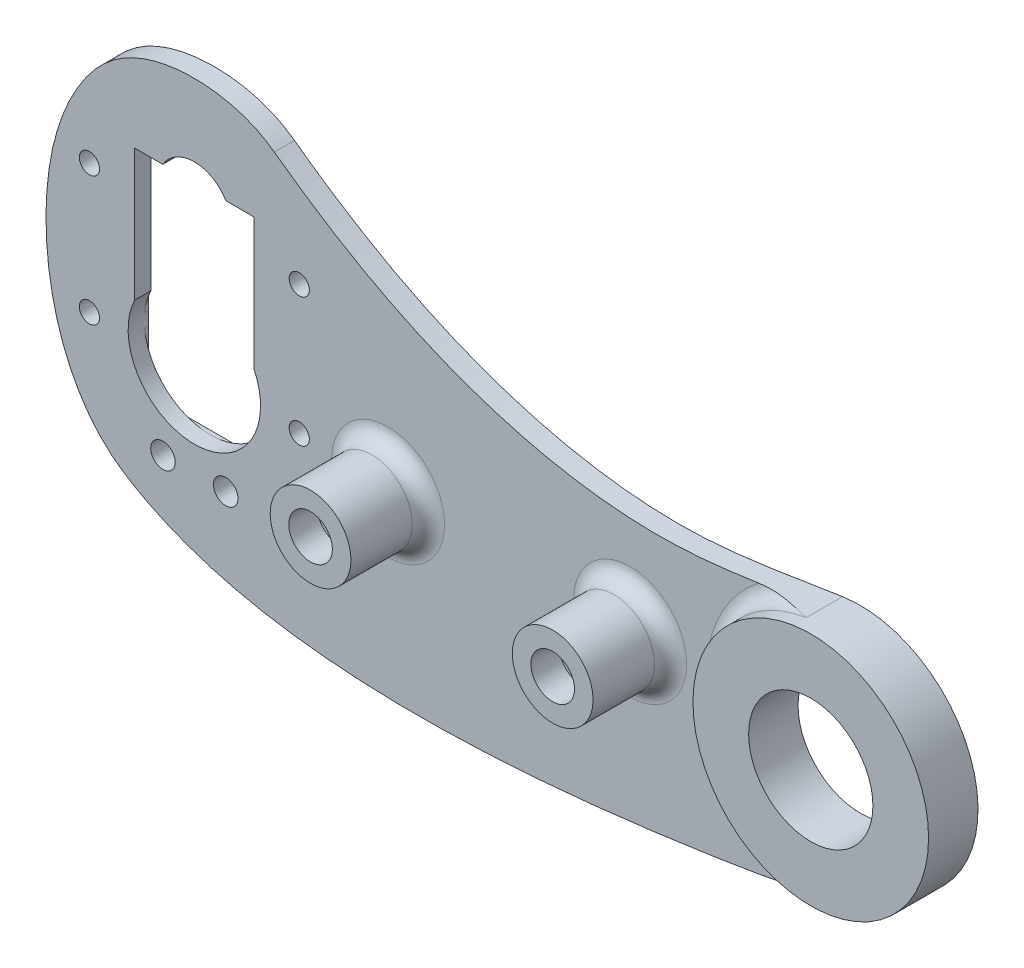
SolidWorks part; units mm, degrees
note: '?' marks a value the reader was unsure of.
ref_plane "Front Plane" through (0, 0, 0) normal (0, 0, 1) x (1, 0, 0)
ref_plane "Top Plane" through (0, 0, 0) normal (0, 1, 0) x (1, 0, 0)
ref_plane "Right Plane" through (0, 0, 0) normal (1, 0, 0) x (0, 0, -1)
sketch "Sketch1" plane through (0, 0, 0) normal (0, 0, 1) x (1, 0, 0)
  line L1 (-59.7576, -2.7999) -> (59.7575, -2.7999) construction
  arc A0 (98.7462, 101.3851) -> (111.9084, 66.5303) centre (101.5997, 82.55) cw
  spline S0 degree 3 poles (12.8847, 120.3395) (20.757, 114.5541) (40.2518, 102.8853) (70.9878, 96.3373) (90.9148, 100.1986) (98.7462, 101.3851) knots 0 0 0 0 0.326633 0.741728 1 1 1 1
  spline S7 degree 3 poles (-11.4525, 64.0459) (8.8535, 50.7358) (59.2076, 53.4213) (104.5778, 61.813) (111.9084, 66.5303) knots 0 0 0 0 0.739683 1 1 1 1
  spline S8 degree 3 poles (-1.8749, 60.7035) (1.8749, 60.7035) (3.711, 60.9284) (5.9539, 61.519) (6.3998, 61.6527) (7.2862, 61.9522) (7.7258, 62.1179) (9.0136, 62.6548) (9.8384, 63.0681) (11.423, 64.0017) (12.1827, 64.5221) (13.2737, 65.3826) (13.6293, 65.6827) (14.3244, 66.3093) (14.6622, 66.6342) (16.2887, 68.2982) (17.41, 69.7686) (18.8777, 72.1399) (19.3317, 72.9613) (20.1584, 74.6261) (20.5332, 75.4725) (21.5561, 78.0488) (22.1035, 79.8152) (22.757, 82.526) (22.9466, 83.4407) (23.269, 85.2688) (23.4024, 86.1848) (23.7252, 88.9383) (23.8375, 90.7812) (23.8583, 93.5559) (23.8405, 94.4825) (23.7536, 96.3394) (23.6842, 97.2698) (23.3967, 100.036) (23.1015, 101.8574) (22.2622, 105.4455) (21.7168, 107.2119) (20.6788, 109.8133) (20.2988, 110.6653) (19.4754, 112.3275) (19.0317, 113.1397) (18.071, 114.7212) (17.555, 115.4909) (16.4308, 116.9762) (15.8182, 117.6943) (13.8675, 119.6805) (12.4021, 120.799) (10.3405, 121.9108) (9.9175, 122.1184) (9.0667, 122.4979) (8.6368, 122.6711) (7.3346, 123.1448) (6.4499, 123.3995) (4.6515, 123.8026) (3.7378, 123.9512) (2.3475, 124.1007) (1.8798, 124.1382) (0.9489, 124.1881) (0.4844, 124.2006) (-0.9061, 124.2017) (-1.8292, 124.1541) (-3.6675, 123.9609) (-4.5827, 123.8155) (-5.9488, 123.513) (-6.4045, 123.3974) (-7.3014, 123.1387) (-7.7438, 122.9953) (-9.0516, 122.5214) (-9.8979, 122.1471) (-11.125, 121.4889) (-11.5269, 121.2534) (-12.316, 120.7487) (-12.7018, 120.4801) (-13.8172, 119.6382) (-14.511, 119.0246) (-15.8096, 117.7038) (-16.4152, 116.9956) (-17.5468, 115.503) (-18.065, 114.7304) (-19.0286, 113.1453) (-19.473, 112.3321) (-20.2967, 110.6699) (-20.6756, 109.8207) (-21.3682, 108.0862) (-21.6789, 107.2076) (-22.2303, 105.4403) (-22.4717, 104.5498) (-23.1011, 101.8593) (-23.3958, 100.0406) (-23.6832, 97.2817) (-23.7525, 96.3567) (-23.8401, 94.4966) (-23.8582, 93.5683) (-23.8381, 90.7933) (-23.7262, 88.9545) (-23.2996, 85.2998) (-22.9853, 83.484) (-22.3374, 80.7801) (-22.0908, 79.8789) (-21.5361, 78.1018) (-21.2287, 77.2271) (-20.2082, 74.6484) (-19.3981, 72.9891) (-17.9359, 70.6142) (-17.4041, 69.8385) (-16.2681, 68.3628) (-15.6623, 67.6597) (-14.3671, 66.3302) (-13.6765, 65.7026) (-12.2066, 64.5387) (-11.4408, 64.013) (-9.8478, 63.0728) (-9.0208, 62.6583) (-7.3047, 61.942) (-6.4104, 61.6395) (-3.7133, 60.9284) (-1.8749, 60.7035) (1.8749, 60.7035) (3.711, 60.9284) knots -0.03125 -0.03125 0 0 0.03125 0.03125 0.039062 0.039062 0.046875 0.046875 0.0625 0.0625 0.078125 0.078125 0.085937 0.085937 0.09375 0.09375 0.125 0.125 0.140625 0.140625 0.15625 0.15625 0.1875 0.1875 0.203125 0.203125 0.21875 0.21875 0.25 0.25 0.265625 0.265625 0.28125 0.28125 0.3125 0.3125 0.34375 0.34375 0.359375 0.359375 0.375 0.375 0.390625 0.390625 0.40625 0.40625 0.4375 0.4375 0.445312 0.445312 0.453125 0.453125 0.46875 0.46875 0.484375 0.484375 0.492187 0.492187 0.5 0.5 0.515625 0.515625 0.53125 0.53125 0.539062 0.539062 0.546875 0.546875 0.5625 0.5625 0.570312 0.570312 0.578125 0.578125 0.59375 0.59375 0.609375 0.609375 0.625 0.625 0.640625 0.640625 0.65625 0.65625 0.671875 0.671875 0.6875 0.6875 0.71875 0.71875 0.734375 0.734375 0.75 0.75 0.78125 0.78125 0.8125 0.8125 0.828125 0.828125 0.84375 0.84375 0.875 0.875 0.890625 0.890625 0.90625 0.90625 0.921875 0.921875 0.9375 0.9375 0.953125 0.953125 0.96875 0.96875 1 1 1.03125 1.03125 1.039062 only from (0, 60.7035) to (0, 60.7035) construction
  spline S9 degree 3 poles (12.8847, 120.3395) (12.2107, 120.8348) (11.5007, 121.2852) (10.3405, 121.9108) (9.9175, 122.1184) (9.0667, 122.4979) (8.6368, 122.6711) (7.3346, 123.1448) (6.4499, 123.3995) (4.6515, 123.8026) (3.7378, 123.9512) (2.3475, 124.1007) (1.8798, 124.1382) (0.9489, 124.1881) (0.4844, 124.2006) (-0.9061, 124.2017) (-1.8292, 124.1541) (-3.6675, 123.9609) (-4.5827, 123.8155) (-5.9488, 123.513) (-6.4045, 123.3974) (-7.3014, 123.1387) (-7.7438, 122.9953) (-9.0516, 122.5214) (-9.8979, 122.1471) (-11.125, 121.4889) (-11.5269, 121.2534) (-12.316, 120.7487) (-12.7018, 120.4801) (-13.8172, 119.6382) (-14.511, 119.0246) (-15.8096, 117.7038) (-16.4152, 116.9956) (-17.5468, 115.503) (-18.065, 114.7304) (-19.0286, 113.1453) (-19.473, 112.3321) (-20.2967, 110.6699) (-20.6756, 109.8207) (-21.3682, 108.0862) (-21.6789, 107.2076) (-22.2303, 105.4403) (-22.4717, 104.5498) (-23.1011, 101.8593) (-23.3958, 100.0406) (-23.6832, 97.2817) (-23.7525, 96.3567) (-23.8401, 94.4966) (-23.8582, 93.5683) (-23.8381, 90.7933) (-23.7262, 88.9545) (-23.2996, 85.2998) (-22.9853, 83.484) (-22.3374, 80.7801) (-22.0908, 79.8789) (-21.5361, 78.1018) (-21.2287, 77.2271) (-20.2082, 74.6484) (-19.3981, 72.9891) (-17.9359, 70.6142) (-17.4041, 69.8385) (-16.2681, 68.3628) (-15.6623, 67.6597) (-14.3671, 66.3302) (-13.6765, 65.7026) (-12.4585, 64.7382) (-11.9621, 64.38) (-11.4525, 64.0459) knots 0.42333 0.42333 0.42333 0.42333 0.4375 0.4375 0.445312 0.445312 0.453125 0.453125 0.46875 0.46875 0.484375 0.484375 0.492187 0.492187 0.5 0.5 0.515625 0.515625 0.53125 0.53125 0.539062 0.539062 0.546875 0.546875 0.5625 0.5625 0.570312 0.570312 0.578125 0.578125 0.59375 0.59375 0.609375 0.609375 0.625 0.625 0.640625 0.640625 0.65625 0.65625 0.671875 0.671875 0.6875 0.6875 0.71875 0.71875 0.734375 0.734375 0.75 0.75 0.78125 0.78125 0.8125 0.8125 0.828125 0.828125 0.84375 0.84375 0.875 0.875 0.890625 0.890625 0.90625 0.90625 0.921875 0.921875 0.932145 0.932145 0.932145 0.932145
  dimension "D1" = 101.6
  dimension "D3" = 19.05
  dimension "D2" = 85.3499
extrude "Boss-Extrude1" add sketch "Sketch1" along normal blind 3.175
hole_wizard "1/8 (0.125) Diameter Hole1" positions "Sketch2" profile "Sketch3" hole size "1/8" standard "ANSI Inch" end condition through all
sketch "Sketch2" plane through (0, 0, 3.175) normal (0, 0, 1) x (1, 0, 0)
  line L0 (0, -8.7367) -> (0, 8.7367) construction
  line L1 (0, 124.201) -> (0, 58.6164) construction
  spline S0 degree 3 poles (12.8847, 120.3395) (12.2107, 120.8348) (11.5007, 121.2852) (10.3405, 121.9108) (9.9175, 122.1184) (9.0667, 122.4979) (8.6368, 122.6711) (7.3346, 123.1448) (6.4499, 123.3995) (4.6515, 123.8026) (3.7378, 123.9512) (2.3475, 124.1007) (1.8798, 124.1382) (0.9489, 124.1881) (0.4844, 124.2006) (-0.9061, 124.2017) (-1.8292, 124.1541) (-3.6675, 123.9609) (-4.5827, 123.8155) (-5.9488, 123.513) (-6.4045, 123.3974) (-7.3014, 123.1387) (-7.7438, 122.9953) (-9.0516, 122.5214) (-9.8979, 122.1471) (-11.125, 121.4889) (-11.5269, 121.2534) (-12.316, 120.7487) (-12.7018, 120.4801) (-13.8172, 119.6382) (-14.511, 119.0246) (-15.8096, 117.7038) (-16.4152, 116.9956) (-17.5468, 115.503) (-18.065, 114.7304) (-19.0286, 113.1453) (-19.473, 112.3321) (-20.2967, 110.6699) (-20.6756, 109.8207) (-21.3682, 108.0862) (-21.6789, 107.2076) (-22.2303, 105.4403) (-22.4717, 104.5498) (-23.1011, 101.8593) (-23.3958, 100.0406) (-23.6832, 97.2817) (-23.7525, 96.3567) (-23.8401, 94.4966) (-23.8582, 93.5683) (-23.8381, 90.7933) (-23.7262, 88.9545) (-23.2996, 85.2998) (-22.9853, 83.484) (-22.3374, 80.7801) (-22.0908, 79.8789) (-21.5361, 78.1018) (-21.2287, 77.2271) (-20.2082, 74.6484) (-19.3981, 72.9891) (-17.9359, 70.6142) (-17.4041, 69.8385) (-16.2681, 68.3628) (-15.6623, 67.6597) (-14.3671, 66.3302) (-13.6765, 65.7026) (-12.4585, 64.7382) (-11.9621, 64.38) (-11.4525, 64.0459) knots 0.42333 0.42333 0.42333 0.42333 0.4375 0.4375 0.445312 0.445312 0.453125 0.453125 0.46875 0.46875 0.484375 0.484375 0.492187 0.492187 0.5 0.5 0.515625 0.515625 0.53125 0.53125 0.539062 0.539062 0.546875 0.546875 0.5625 0.5625 0.570312 0.570312 0.578125 0.578125 0.59375 0.59375 0.609375 0.609375 0.625 0.625 0.640625 0.640625 0.65625 0.65625 0.671875 0.671875 0.6875 0.6875 0.71875 0.71875 0.734375 0.734375 0.75 0.75 0.78125 0.78125 0.8125 0.8125 0.828125 0.828125 0.84375 0.84375 0.875 0.875 0.890625 0.890625 0.90625 0.90625 0.921875 0.921875 0.932145 0.932145 0.932145 0.932145 construction
  spline S1 degree 3 poles (-11.4525, 64.0459) (8.8535, 50.7358) (59.2076, 53.4213) (104.5778, 61.813) (111.9084, 66.5303) knots 0 0 0 0 0.739683 1 1 1 1 construction
  point P28 (16.51, 103.881)
  point P30 (16.51, 83.561)
  point P32 (-16.51, 83.561)
  point P61 (-16.51, 103.881)
  dimension "D1" = 16.51
  dimension "D2" = 20.32
  dimension "D3" = 16.51
  dimension "D4" = 20.32
sketch "Sketch3" plane through (-16.51, 103.881, 3.175) normal (1, 0, 0) x (0, -1, 0)
  line L0 (0, 0) -> (0, 3.175)
  line L1 (0, 3.175) -> (1.5875, 3.175)
  line L2 (1.5875, 3.175) -> (1.5875, 0)
  line L5 (1.5875, 0) -> (0, 0)
  line L11 (0, -6.35) -> (0, 107.95) construction
  dimension "Thru Hole Dia." = 3.175
  dimension "Thru Hole Depth" = 3.175
sketch "Sketch7" plane through (0, 0, 0) normal (0, 0, -1) x (-1, 0, 0)
  line L1 (9.0932, 115.311) -> (-9.0932, 115.311)
  line L2 (10.3632, 114.041) -> (10.3632, 75.1028)
  line L3 (9.0932, 73.8328) -> (-9.0932, 73.8328)
  line L4 (-10.3632, 114.041) -> (-10.3632, 75.1028)
  line L5 (0, 124.201) -> (0, 60.7035) construction
  line L6 (0, 8.7367) -> (0, -8.7367) construction
  arc A0 (9.0932, 115.311) -> (10.3632, 114.041) centre (9.0932, 114.041) cw
  arc A1 (10.3632, 75.1028) -> (9.0932, 73.8328) centre (9.0932, 75.1028) cw
  arc A2 (-9.0932, 73.8328) -> (-10.3632, 75.1028) centre (-9.0932, 75.1028) cw
  arc A3 (-9.0932, 115.311) -> (-10.3632, 114.041) centre (-9.0932, 114.041) ccw
  spline S0 degree 3 poles (-12.8847, 120.3395) (-12.2107, 120.8348) (-11.5007, 121.2852) (-10.3405, 121.9108) (-9.9175, 122.1184) (-9.0667, 122.4979) (-8.6368, 122.6711) (-7.3346, 123.1448) (-6.4499, 123.3995) (-4.6515, 123.8026) (-3.7378, 123.9512) (-2.3475, 124.1007) (-1.8798, 124.1382) (-0.9489, 124.1881) (-0.4844, 124.2006) (0.9061, 124.2017) (1.8292, 124.1541) (3.6675, 123.9609) (4.5827, 123.8155) (5.9488, 123.513) (6.4045, 123.3974) (7.3014, 123.1387) (7.7438, 122.9953) (9.0516, 122.5214) (9.8979, 122.1471) (11.125, 121.4889) (11.5269, 121.2534) (12.316, 120.7487) (12.7018, 120.4801) (13.8172, 119.6382) (14.511, 119.0246) (15.8096, 117.7038) (16.4152, 116.9956) (17.5468, 115.503) (18.065, 114.7304) (19.0286, 113.1453) (19.473, 112.3321) (20.2967, 110.6699) (20.6756, 109.8207) (21.3682, 108.0862) (21.6789, 107.2076) (22.2303, 105.4403) (22.4717, 104.5498) (23.1011, 101.8593) (23.3958, 100.0406) (23.6832, 97.2817) (23.7525, 96.3567) (23.8401, 94.4966) (23.8582, 93.5683) (23.8381, 90.7933) (23.7262, 88.9545) (23.2996, 85.2998) (22.9853, 83.484) (22.3374, 80.7801) (22.0908, 79.8789) (21.5361, 78.1018) (21.2287, 77.2271) (20.2082, 74.6484) (19.3981, 72.9891) (17.9359, 70.6142) (17.4041, 69.8385) (16.2681, 68.3628) (15.6623, 67.6597) (14.3671, 66.3302) (13.6765, 65.7026) (12.4585, 64.7382) (11.9621, 64.38) (11.4525, 64.0459) knots 0.42333 0.42333 0.42333 0.42333 0.4375 0.4375 0.445312 0.445312 0.453125 0.453125 0.46875 0.46875 0.484375 0.484375 0.492187 0.492187 0.5 0.5 0.515625 0.515625 0.53125 0.53125 0.539062 0.539062 0.546875 0.546875 0.5625 0.5625 0.570312 0.570312 0.578125 0.578125 0.59375 0.59375 0.609375 0.609375 0.625 0.625 0.640625 0.640625 0.65625 0.65625 0.671875 0.671875 0.6875 0.6875 0.71875 0.71875 0.734375 0.734375 0.75 0.75 0.78125 0.78125 0.8125 0.8125 0.828125 0.828125 0.84375 0.84375 0.875 0.875 0.890625 0.890625 0.90625 0.90625 0.921875 0.921875 0.932145 0.932145 0.932145 0.932145 construction
  spline S2 degree 3 poles (-1.8749, 60.7035) (1.8749, 60.7035) (3.7133, 60.9284) (6.4104, 61.6395) (7.3047, 61.942) (9.0208, 62.6583) (9.8478, 63.0728) (11.4408, 64.013) (12.2066, 64.5387) (13.6765, 65.7026) (14.3671, 66.3302) (15.6623, 67.6597) (16.2681, 68.3628) (17.4041, 69.8385) (17.9359, 70.6142) (19.3981, 72.9891) (20.2082, 74.6484) (21.2287, 77.2271) (21.5361, 78.1018) (22.0908, 79.8789) (22.3374, 80.7801) (22.9853, 83.484) (23.2996, 85.2998) (23.7262, 88.9545) (23.8381, 90.7933) (23.8582, 93.5683) (23.8401, 94.4966) (23.7525, 96.3567) (23.6832, 97.2817) (23.3958, 100.0406) (23.1011, 101.8593) (22.4717, 104.5498) (22.2303, 105.4403) (21.6789, 107.2076) (21.3682, 108.0862) (20.6756, 109.8207) (20.2967, 110.6699) (19.473, 112.3321) (19.0286, 113.1453) (18.065, 114.7304) (17.5468, 115.503) (16.4152, 116.9956) (15.8096, 117.7038) (14.511, 119.0246) (13.8172, 119.6382) (12.7018, 120.4801) (12.316, 120.7487) (11.5269, 121.2534) (11.125, 121.4889) (9.8979, 122.1471) (9.0516, 122.5214) (7.7438, 122.9953) (7.3014, 123.1387) (6.4045, 123.3974) (5.9488, 123.513) (4.5827, 123.8155) (3.6675, 123.9609) (1.8292, 124.1541) (0.9061, 124.2017) (-0.4844, 124.2006) (-0.9489, 124.1881) (-1.8798, 124.1382) (-2.3475, 124.1007) (-3.7378, 123.9512) (-4.6515, 123.8026) (-6.4499, 123.3995) (-7.3346, 123.1448) (-8.6368, 122.6711) (-9.0667, 122.4979) (-9.9175, 122.1184) (-10.3405, 121.9108) (-12.4021, 120.799) (-13.8675, 119.6805) (-15.8182, 117.6943) (-16.4308, 116.9762) (-17.555, 115.4909) (-18.071, 114.7212) (-19.0317, 113.1397) (-19.4754, 112.3275) (-20.2988, 110.6653) (-20.6788, 109.8133) (-21.7168, 107.2119) (-22.2622, 105.4455) (-23.1015, 101.8574) (-23.3967, 100.036) (-23.6842, 97.2698) (-23.7536, 96.3394) (-23.8405, 94.4825) (-23.8583, 93.5559) (-23.8375, 90.7812) (-23.7252, 88.9383) (-23.4024, 86.1848) (-23.269, 85.2688) (-22.9466, 83.4407) (-22.757, 82.526) (-22.1035, 79.8152) (-21.5561, 78.0488) (-20.5332, 75.4725) (-20.1584, 74.6261) (-19.3317, 72.9613) (-18.8777, 72.1399) (-17.41, 69.7686) (-16.2887, 68.2982) (-14.6622, 66.6342) (-14.3244, 66.3093) (-13.6293, 65.6827) (-13.2737, 65.3826) (-12.1827, 64.5221) (-11.423, 64.0017) (-9.8384, 63.0681) (-9.0136, 62.6548) (-7.7258, 62.1179) (-7.2862, 61.9522) (-6.3998, 61.6527) (-5.9539, 61.519) (-3.711, 60.9284) (-1.8749, 60.7035) (1.8749, 60.7035) (3.7133, 60.9284) knots -0.03125 -0.03125 0 0 0.03125 0.03125 0.046875 0.046875 0.0625 0.0625 0.078125 0.078125 0.09375 0.09375 0.109375 0.109375 0.125 0.125 0.15625 0.15625 0.171875 0.171875 0.1875 0.1875 0.21875 0.21875 0.25 0.25 0.265625 0.265625 0.28125 0.28125 0.3125 0.3125 0.328125 0.328125 0.34375 0.34375 0.359375 0.359375 0.375 0.375 0.390625 0.390625 0.40625 0.40625 0.421875 0.421875 0.429688 0.429688 0.4375 0.4375 0.453125 0.453125 0.460938 0.460938 0.46875 0.46875 0.484375 0.484375 0.5 0.5 0.507813 0.507813 0.515625 0.515625 0.53125 0.53125 0.546875 0.546875 0.554688 0.554688 0.5625 0.5625 0.59375 0.59375 0.609375 0.609375 0.625 0.625 0.640625 0.640625 0.65625 0.65625 0.6875 0.6875 0.71875 0.71875 0.734375 0.734375 0.75 0.75 0.78125 0.78125 0.796875 0.796875 0.8125 0.8125 0.84375 0.84375 0.859375 0.859375 0.875 0.875 0.90625 0.90625 0.914063 0.914063 0.921875 0.921875 0.9375 0.9375 0.953125 0.953125 0.960938 0.960938 0.96875 0.96875 1 1 1.03125 1.03125 1.046875 only from (0, 60.7035) to (0, 60.7035) construction
  point P24 (0, 115.311)
  dimension "D3" = 1.27
  dimension "D1" = 41.4782
  dimension "D2" = 20.7264
  dimension "D4" = 8.89
extrude "Cut-Extrude3" cut sketch "Sketch7" against normal blind 0.635
sketch "Sketch8" plane through (0, 0, 3.175) normal (0, 0, 1) x (1, 0, 0)
  line L0 (0, -8.7367) -> (0, 8.7367) construction
  line L1 (-9.0932, 73.8328) -> (9.0932, 73.8328) construction
  line L20 (-4.9585, 109.4888) -> (-9.388, 109.4888)
  line L21 (-9.388, 109.4888) -> (-9.388, 88.7675)
  line L22 (9.388, 88.7675) -> (9.388, 109.4888)
  line L23 (9.388, 109.4888) -> (4.9585, 109.4888)
  arc A13 (-9.388, 88.7675) -> (9.388, 88.7675) centre (0, 84.2508) ccw
  arc A14 (4.9585, 109.4888) -> (-4.9585, 109.4888) centre (0, 106.5508) ccw
  dimension "D1" = 5.7635
  dimension "D2" = 10.418
  dimension "D3" = 25.238
  dimension "D4" = 18.776
  dimension "D5" = 2.938
extrude "Cut-Extrude4" cut sketch "Sketch8" against normal through all
sketch "Sketch10" plane through (0, 0, 0) normal (0, 0, -1) x (-1, 0, 0)
  circle A0 centre (-101.5997, 82.55) radius 9.779
  dimension "D1" = 19.558
extrude "Cut-Extrude5" cut sketch "Sketch10" against normal through all
hole_wizard "Hole1" positions "Sketch12" profile "Sketch13" legacy
sketch "Sketch12" plane through (0, 0, 0) normal (0, 0, -1) x (-1, 0, 0)
  point P0 (-4.935, 69.8508)
  point P3 (4.935, 69.8508)
sketch "Sketch13" plane through (4.935, 69.8508, 0) normal (1, 0, 0) x (0, 1, 0)
  line L0 (0, 0) -> (0, 8.255)
  line L1 (0, 8.255) -> (1.5875, 8.255)
  line L2 (1.5875, 8.255) -> (1.5875, 5.1562)
  line L3 (1.5875, 5.1562) -> (1.9304, 5.1562)
  line L4 (1.9304, 5.1562) -> (1.9304, 0)
  line L5 (1.9304, 0) -> (0, 0)
  line L6 (0, 110) -> (0, -10) construction
  dimension "Diameter" = 3.175
  dimension "Depth" = 8.255
  dimension "C-Bore Diameter" = 3.8608
  dimension "C-Bore Depth" = 5.1562
sketch "Sketch16" plane through (0, 0, 0) normal (0, 0, -1) x (-1, 0, 0)
  arc A1 (-98.7462, 101.3851) -> (-111.9084, 66.5303) centre (-101.5997, 82.55) ccw construction
  arc A2 (-98.8223, 100.8828) -> (-111.6335, 66.9574) centre (-101.5997, 82.55) ccw
  arc A3 (-98.8223, 100.8828) -> (-111.6335, 66.9574) centre (-101.5997, 82.55) ccw
  arc A4 (-98.7462, 101.3851) -> (-111.9084, 66.5303) centre (-101.5997, 82.55) ccw
  spline S3 degree 3 poles (1.8749, 60.7035) (-1.8749, 60.7035) (-3.711, 60.9284) (-5.9539, 61.519) (-6.3998, 61.6527) (-7.2862, 61.9522) (-7.7258, 62.1179) (-9.0136, 62.6548) (-9.8384, 63.0681) (-11.423, 64.0017) (-12.1827, 64.5221) (-13.2737, 65.3826) (-13.6293, 65.6827) (-14.3244, 66.3093) (-14.6622, 66.6342) (-16.2887, 68.2982) (-17.41, 69.7686) (-18.8777, 72.1399) (-19.3317, 72.9613) (-20.1584, 74.6261) (-20.5332, 75.4725) (-21.5561, 78.0488) (-22.1035, 79.8152) (-22.757, 82.526) (-22.9466, 83.4407) (-23.269, 85.2688) (-23.4024, 86.1848) (-23.7252, 88.9383) (-23.8375, 90.7812) (-23.8583, 93.5559) (-23.8405, 94.4825) (-23.7536, 96.3394) (-23.6842, 97.2698) (-23.3967, 100.036) (-23.1015, 101.8574) (-22.2622, 105.4455) (-21.7168, 107.2119) (-20.6788, 109.8133) (-20.2988, 110.6653) (-19.4754, 112.3275) (-19.0317, 113.1397) (-18.071, 114.7212) (-17.555, 115.4909) (-16.4308, 116.9762) (-15.8182, 117.6943) (-13.8675, 119.6805) (-12.4021, 120.799) (-10.3405, 121.9108) (-9.9175, 122.1184) (-9.0667, 122.4979) (-8.6368, 122.6711) (-7.3346, 123.1448) (-6.4499, 123.3995) (-4.6515, 123.8026) (-3.7378, 123.9512) (-2.3475, 124.1007) (-1.8798, 124.1382) (-0.9489, 124.1881) (-0.4844, 124.2006) (0.9061, 124.2017) (1.8292, 124.1541) (3.6675, 123.9609) (4.5827, 123.8155) (5.9488, 123.513) (6.4045, 123.3974) (7.3014, 123.1387) (7.7438, 122.9953) (9.0516, 122.5214) (9.8979, 122.1471) (11.125, 121.4889) (11.5269, 121.2534) (12.316, 120.7487) (12.7018, 120.4801) (13.8172, 119.6382) (14.511, 119.0246) (15.8096, 117.7038) (16.4152, 116.9956) (17.5468, 115.503) (18.065, 114.7304) (19.0286, 113.1453) (19.473, 112.3321) (20.2967, 110.6699) (20.6756, 109.8207) (21.3682, 108.0862) (21.6789, 107.2076) (22.2303, 105.4403) (22.4717, 104.5498) (23.1011, 101.8593) (23.3958, 100.0406) (23.6832, 97.2817) (23.7525, 96.3567) (23.8401, 94.4966) (23.8582, 93.5683) (23.8381, 90.7933) (23.7262, 88.9545) (23.2996, 85.2998) (22.9853, 83.484) (22.3374, 80.7801) (22.0908, 79.8789) (21.5361, 78.1018) (21.2287, 77.2271) (20.2082, 74.6484) (19.3981, 72.9891) (17.9359, 70.6142) (17.4041, 69.8385) (16.2681, 68.3628) (15.6623, 67.6597) (14.3671, 66.3302) (13.6765, 65.7026) (12.2066, 64.5387) (11.4408, 64.013) (9.8478, 63.0728) (9.0208, 62.6583) (7.3047, 61.942) (6.4104, 61.6395) (3.7133, 60.9284) (1.8749, 60.7035) (-1.8749, 60.7035) (-3.711, 60.9284) knots -0.03125 -0.03125 0 0 0.03125 0.03125 0.039062 0.039062 0.046875 0.046875 0.0625 0.0625 0.078125 0.078125 0.085937 0.085937 0.09375 0.09375 0.125 0.125 0.140625 0.140625 0.15625 0.15625 0.1875 0.1875 0.203125 0.203125 0.21875 0.21875 0.25 0.25 0.265625 0.265625 0.28125 0.28125 0.3125 0.3125 0.34375 0.34375 0.359375 0.359375 0.375 0.375 0.390625 0.390625 0.40625 0.40625 0.4375 0.4375 0.445312 0.445312 0.453125 0.453125 0.46875 0.46875 0.484375 0.484375 0.492187 0.492187 0.5 0.5 0.515625 0.515625 0.53125 0.53125 0.539062 0.539062 0.546875 0.546875 0.5625 0.5625 0.570312 0.570312 0.578125 0.578125 0.59375 0.59375 0.609375 0.609375 0.625 0.625 0.640625 0.640625 0.65625 0.65625 0.671875 0.671875 0.6875 0.6875 0.71875 0.71875 0.734375 0.734375 0.75 0.75 0.78125 0.78125 0.8125 0.8125 0.828125 0.828125 0.84375 0.84375 0.875 0.875 0.890625 0.890625 0.90625 0.90625 0.921875 0.921875 0.9375 0.9375 0.953125 0.953125 0.96875 0.96875 1 1 1.03125 1.03125 1.039062 only from (-12.8847, 120.3395) to (11.4525, 64.0459) construction
  spline S4 degree 3 poles (-774.2713, -1774.5433) (-240.5791, 269.0945) (-155.3516, 78.3647) (119.4613, 136.9101) (90.2802, 612.3789) (-467.9203, -1827.1495) knots -2.744785 -2.744785 -2.744785 -2.744785 0.258272 0.673367 6.196281 6.196281 6.196281 6.196281 only from (-98.7462, 101.3851) to (-12.8847, 120.3395) construction
  spline S5 degree 3 poles (-1432.2891, 1438.8419) (302.1687, 78.3883) (-46.8302, 8.2524) (-247.2516, 108.2293) (1573.9405, 1138.8243) knots -2.721752 -2.721752 -2.721752 -2.721752 0.739683 2.738287 2.738287 2.738287 2.738287 only from (11.4525, 64.0459) to (-111.9084, 66.5303) construction
  spline S6 degree 3 poles (-2189.0847, 2099.4129) (-262.4106, 170.4677) (-28.1678, 19.131) (15.6659, 68.4561) (15.964, 68.8125) (16.5416, 69.5447) (16.8215, 69.9212) (17.625, 71.0645) (18.1161, 71.8495) (19.4736, 74.2635) (20.2235, 75.952) (21.0047, 78.1423) (21.1532, 78.5852) (21.4331, 79.4725) (21.5646, 79.9175) (21.9359, 81.2558) (22.1523, 82.1528) (22.7169, 84.8568) (22.9808, 86.6766) (23.227, 89.4293) (23.2837, 90.3507) (23.3467, 92.2012) (23.3532, 93.1331) (23.2962, 95.9153) (23.1579, 97.7528) (22.6664, 101.3907) (22.3118, 103.1909) (21.5787, 105.8563) (21.3007, 106.739) (20.8285, 108.0535) (20.6616, 108.4909) (20.3114, 109.3557) (20.128, 109.7836) (19.5526, 111.0538) (19.1362, 111.8829) (18.2322, 113.5028) (17.7449, 114.2937) (16.9487, 115.445) (16.6714, 115.8238) (16.0972, 116.5601) (15.8001, 116.9181) (14.876, 117.9587) (14.2159, 118.6078) (13.1501, 119.5046) (12.7822, 119.7907) (12.0198, 120.3359) (11.6269, 120.5937) (10.4299, 121.3129) (9.6011, 121.7248) (8.316, 122.2507) (7.8807, 122.4106) (6.9967, 122.7012) (6.5467, 122.8322) (5.1865, 123.1808) (4.2742, 123.353) (2.4403, 123.5949) (1.5188, 123.6652) (0.1298, 123.6968) (-0.3342, 123.695) (-1.2647, 123.6664) (-1.7324, 123.6393) (-3.1284, 123.5203) (-4.0462, 123.3914) (-5.8547, 123.0273) (-6.7453, 122.7922) (-8.0574, 122.347) (-8.4908, 122.1832) (-9.349, 121.8219) (-9.7752, 121.6237) (-90.4408, 80.1939) (184.1635, -546.8682) (1304.7176, -2570.5597) knots -2.147593 -2.147593 -2.147593 -2.147593 0.0625 0.0625 0.078125 0.078125 0.09375 0.09375 0.125 0.125 0.1875 0.1875 0.203125 0.203125 0.21875 0.21875 0.25 0.25 0.3125 0.3125 0.34375 0.34375 0.375 0.375 0.4375 0.4375 0.5 0.5 0.53125 0.53125 0.546875 0.546875 0.5625 0.5625 0.59375 0.59375 0.625 0.625 0.640625 0.640625 0.65625 0.65625 0.6875 0.6875 0.703125 0.703125 0.71875 0.71875 0.75 0.75 0.765625 0.765625 0.78125 0.78125 0.8125 0.8125 0.84375 0.84375 0.859375 0.859375 0.875 0.875 0.90625 0.90625 0.9375 0.9375 0.953125 0.953125 0.96875 0.96875 3.969871 3.969871 3.969871 3.969871 only from (11.174, 64.4708) to (-12.5838, 119.9301)
  spline S7 degree 3 poles (2048.6103, -1983.426) (58.7248, 829.8593) (166.9256, 229.9139) (-23.7272, 112.5017) (-25.3772, 111.5351) (-28.7252, 109.6798) (-30.4244, 108.7904) (-35.592, 106.2537) (-39.095, 104.7565) (-46.2251, 102.1769) (-49.851, 101.091) (-55.3885, 99.7916) (-57.2508, 99.4137) (-60.0708, 98.9354) (-61.0153, 98.7908) (-62.9133, 98.5324) (-63.8683, 98.4185) (-68.6518, 97.9313) (-72.4591, 97.8086) (-179.3835, 102.4579) (-267.4227, 313.3667) (-602.151, -2848.3137) knots -7.132024 -7.132024 -7.132024 -7.132024 0.125 0.125 0.1875 0.1875 0.25 0.25 0.375 0.375 0.5 0.5 0.5625 0.5625 0.59375 0.59375 0.625 0.625 0.75 0.75 4.155026 4.155026 4.155026 4.155026 only from (-12.5838, 119.9301) to (-98.8223, 100.8828)
  spline S8 degree 3 poles (673.853, 2960.0442) (-168.6133, 212.6667) (-155.2694, 87.1083) (-106.9518, 64.4911) (-105.74, 64.0012) (-103.2866, 63.1129) (-102.0449, 62.7149) (-99.5398, 61.9849) (-98.2764, 61.6531) (-94.4623, 60.7311) (-91.8866, 60.2126) (-86.7077, 59.2798) (-84.112, 58.8676) (-76.317, 57.6978) (-71.1112, 56.9962) (-60.6752, 55.803) (-55.4449, 55.3117) (-47.5738, 54.7964) (-44.9429, 54.6617) (-39.6919, 54.4826) (-37.0705, 54.4379) (-31.8374, 54.4562) (-29.2258, 54.519) (-24.0146, 54.776) (-21.4149, 54.97) (-16.2307, 55.5229) (-13.6461, 55.8814) (-8.4964, 56.813) (-5.9312, 57.3853) (-2.1037, 58.4645) (-0.8268, 58.8631) (1.6873, 59.7383) (2.9262, 60.2151) (81.3748, 93.829) (75.8831, 305.7868) (-1020.3508, 2876.1977) knots -1.206471 -1.206471 -1.206471 -1.206471 0.03125 0.03125 0.0625 0.0625 0.09375 0.09375 0.125 0.125 0.1875 0.1875 0.25 0.25 0.375 0.375 0.5 0.5 0.5625 0.5625 0.625 0.625 0.6875 0.6875 0.75 0.75 0.8125 0.8125 0.875 0.875 0.90625 0.90625 0.9375 0.9375 2.918904 2.918904 2.918904 2.918904 only from (-111.6335, 66.9574) to (11.174, 64.4708)
  spline S9 degree 3 poles (11.174, 64.4708) (12.7439, 65.4998) (14.1273, 66.7247) (15.6659, 68.4561) (15.964, 68.8125) (16.5416, 69.5447) (16.8215, 69.9212) (17.625, 71.0645) (18.1161, 71.8495) (19.4736, 74.2635) (20.2235, 75.952) (21.0047, 78.1423) (21.1532, 78.5852) (21.4331, 79.4725) (21.5646, 79.9175) (21.9359, 81.2558) (22.1523, 82.1528) (22.7169, 84.8568) (22.9808, 86.6766) (23.227, 89.4293) (23.2837, 90.3507) (23.3467, 92.2012) (23.3532, 93.1331) (23.2962, 95.9153) (23.1579, 97.7528) (22.6664, 101.3907) (22.3118, 103.1909) (21.5787, 105.8563) (21.3007, 106.739) (20.8285, 108.0535) (20.6616, 108.4909) (20.3114, 109.3557) (20.128, 109.7836) (19.5526, 111.0538) (19.1362, 111.8829) (18.2322, 113.5028) (17.7449, 114.2937) (16.9487, 115.445) (16.6714, 115.8238) (16.0972, 116.5601) (15.8001, 116.9181) (14.876, 117.9587) (14.2159, 118.6078) (13.1501, 119.5046) (12.7822, 119.7907) (12.0198, 120.3359) (11.6269, 120.5937) (10.4299, 121.3129) (9.6011, 121.7248) (8.316, 122.2507) (7.8807, 122.4106) (6.9967, 122.7012) (6.5467, 122.8322) (5.1865, 123.1808) (4.2742, 123.353) (2.4403, 123.5949) (1.5188, 123.6652) (0.1298, 123.6968) (-0.3342, 123.695) (-1.2647, 123.6664) (-1.7324, 123.6393) (-3.1284, 123.5203) (-4.0462, 123.3914) (-5.8547, 123.0273) (-6.7453, 122.7922) (-8.0574, 122.347) (-8.4908, 122.1832) (-9.349, 121.8219) (-9.7752, 121.6237) (-11.0286, 120.9799) (-11.8257, 120.4872) (-12.5838, 119.9301) knots 0 0 0 0 0.0625 0.0625 0.078125 0.078125 0.09375 0.09375 0.125 0.125 0.1875 0.1875 0.203125 0.203125 0.21875 0.21875 0.25 0.25 0.3125 0.3125 0.34375 0.34375 0.375 0.375 0.4375 0.4375 0.5 0.5 0.53125 0.53125 0.546875 0.546875 0.5625 0.5625 0.59375 0.59375 0.625 0.625 0.640625 0.640625 0.65625 0.65625 0.6875 0.6875 0.703125 0.703125 0.71875 0.71875 0.75 0.75 0.765625 0.765625 0.78125 0.78125 0.8125 0.8125 0.84375 0.84375 0.859375 0.859375 0.875 0.875 0.90625 0.90625 0.9375 0.9375 0.953125 0.953125 0.96875 0.96875 1 1 1 1
  spline S10 degree 3 poles (-12.5838, 119.9301) (-15.6756, 117.658) (-18.8433, 115.5094) (-23.7272, 112.5017) (-25.3772, 111.5351) (-28.7252, 109.6798) (-30.4244, 108.7904) (-35.592, 106.2537) (-39.095, 104.7565) (-46.2251, 102.1769) (-49.851, 101.091) (-55.3885, 99.7916) (-57.2508, 99.4137) (-60.0708, 98.9354) (-61.0153, 98.7908) (-62.9133, 98.5324) (-63.8683, 98.4185) (-68.6518, 97.9313) (-72.4591, 97.8086) (-83.8178, 98.3025) (-91.3089, 99.7445) (-98.8223, 100.8828) knots 0 0 0 0 0.125 0.125 0.1875 0.1875 0.25 0.25 0.375 0.375 0.5 0.5 0.5625 0.5625 0.59375 0.59375 0.625 0.625 0.75 0.75 1 1 1 1
  spline S11 degree 3 poles (-111.6335, 66.9574) (-110.4999, 66.228) (-109.3316, 65.605) (-106.9518, 64.4911) (-105.74, 64.0012) (-103.2866, 63.1129) (-102.0449, 62.7149) (-99.5398, 61.9849) (-98.2764, 61.6531) (-94.4623, 60.7311) (-91.8866, 60.2126) (-86.7077, 59.2798) (-84.112, 58.8676) (-76.317, 57.6978) (-71.1112, 56.9962) (-60.6752, 55.803) (-55.4449, 55.3117) (-47.5738, 54.7964) (-44.9429, 54.6617) (-39.6919, 54.4826) (-37.0705, 54.4379) (-31.8374, 54.4562) (-29.2258, 54.519) (-24.0146, 54.776) (-21.4149, 54.97) (-16.2307, 55.5229) (-13.6461, 55.8814) (-8.4964, 56.813) (-5.9312, 57.3853) (-2.1037, 58.4645) (-0.8268, 58.8631) (1.6873, 59.7383) (2.9262, 60.2151) (6.5803, 61.7808) (8.9341, 63.0026) (11.174, 64.4708) knots 0 0 0 0 0.03125 0.03125 0.0625 0.0625 0.09375 0.09375 0.125 0.125 0.1875 0.1875 0.25 0.25 0.375 0.375 0.5 0.5 0.5625 0.5625 0.625 0.625 0.6875 0.6875 0.75 0.75 0.8125 0.8125 0.875 0.875 0.90625 0.90625 0.9375 0.9375 1 1 1 1
  spline S12 degree 3 poles (-12.8847, 120.3395) (-12.2107, 120.8348) (-11.5007, 121.2852) (-10.3405, 121.9108) (-9.9175, 122.1184) (-9.0667, 122.4979) (-8.6368, 122.6711) (-7.3346, 123.1448) (-6.4499, 123.3995) (-4.6515, 123.8026) (-3.7378, 123.9512) (-2.3475, 124.1007) (-1.8798, 124.1382) (-0.9489, 124.1881) (-0.4844, 124.2006) (0.9061, 124.2017) (1.8292, 124.1541) (3.6675, 123.9609) (4.5827, 123.8155) (5.9488, 123.513) (6.4045, 123.3974) (7.3014, 123.1387) (7.7438, 122.9953) (9.0516, 122.5214) (9.8979, 122.1471) (11.125, 121.4889) (11.5269, 121.2534) (12.316, 120.7487) (12.7018, 120.4801) (13.8172, 119.6382) (14.511, 119.0246) (15.8096, 117.7038) (16.4152, 116.9956) (17.5468, 115.503) (18.065, 114.7304) (19.0286, 113.1453) (19.473, 112.3321) (20.2967, 110.6699) (20.6756, 109.8207) (21.3682, 108.0862) (21.6789, 107.2076) (22.2303, 105.4403) (22.4717, 104.5498) (23.1011, 101.8593) (23.3958, 100.0406) (23.6832, 97.2817) (23.7525, 96.3567) (23.8401, 94.4966) (23.8582, 93.5683) (23.8381, 90.7933) (23.7262, 88.9545) (23.2996, 85.2998) (22.9853, 83.484) (22.3374, 80.7801) (22.0908, 79.8789) (21.5361, 78.1018) (21.2287, 77.2271) (20.2082, 74.6484) (19.3981, 72.9891) (17.9359, 70.6142) (17.4041, 69.8385) (16.2681, 68.3628) (15.6623, 67.6597) (14.3671, 66.3302) (13.6765, 65.7026) (12.4585, 64.7382) (11.9621, 64.38) (11.4525, 64.0459) knots 0.42333 0.42333 0.42333 0.42333 0.4375 0.4375 0.445312 0.445312 0.453125 0.453125 0.46875 0.46875 0.484375 0.484375 0.492187 0.492187 0.5 0.5 0.515625 0.515625 0.53125 0.53125 0.539062 0.539062 0.546875 0.546875 0.5625 0.5625 0.570312 0.570312 0.578125 0.578125 0.59375 0.59375 0.609375 0.609375 0.625 0.625 0.640625 0.640625 0.65625 0.65625 0.671875 0.671875 0.6875 0.6875 0.71875 0.71875 0.734375 0.734375 0.75 0.75 0.78125 0.78125 0.8125 0.8125 0.828125 0.828125 0.84375 0.84375 0.875 0.875 0.890625 0.890625 0.90625 0.90625 0.921875 0.921875 0.932145 0.932145 0.932145 0.932145
  spline S13 degree 3 poles (-98.7462, 101.3851) (-90.9148, 100.1986) (-70.9878, 96.3373) (-40.2518, 102.8853) (-20.757, 114.5541) (-12.8847, 120.3395) knots 0 0 0 0 0.258272 0.673367 1 1 1 1
  spline S14 degree 3 poles (11.4525, 64.0459) (-8.8535, 50.7358) (-59.2076, 53.4213) (-104.5778, 61.813) (-111.9084, 66.5303) knots 0 0 0 0 0.739683 1 1 1 1
  dimension "D1" = 0.508
extrude "Cut-Extrude7" cut sketch "Sketch16" against normal through all
sketch "Sketch14" plane through (0, 0, 3.175) normal (0, 0, 1) x (1, 0, 0)
  circle A0 centre (101.5997, 82.55) radius 18.542
  circle A2 centre (101.5997, 82.55) radius 9.779
  circle A3 centre (101.5997, 82.55) radius 9.779 construction
  arc A5 (111.6335, 66.9574) -> (98.8223, 100.8828) centre (101.5997, 82.55) ccw construction
extrude "Boss-Extrude3" add sketch "Sketch14" along normal blind 4.6037
ref_axis "Axis1" through (0, 84.2508, 3.175) along (0.9994, -0.0167, -0.0312)?
sketch "Sketch18" plane through (0, 0, 3.175) normal (0, 0, 1) x (1, 0, 0)
  line L0 (101.5997, 82.55) -> (20.3632, 82.55) construction
  circle A1 centre (30.4797, 82.55) radius 6.35
  circle A2 centre (68.5797, 82.55) radius 6.35
  circle A5 centre (101.5997, 82.55) radius 9.779 construction
  dimension "D1" = 12.7
  dimension "D2" = 12.7
  dimension "D3" = 38.1
  dimension "D4" = 33.02
extrude "Boss-Extrude4" add sketch "Sketch18" along normal blind 12.192
sketch "Sketch19" plane through (0, 0, 15.367) normal (0, 0, 1) x (1, 0, 0)
  circle A0 centre (30.4797, 82.55) radius 3.429
  circle A1 centre (68.5797, 82.55) radius 3.429
  dimension "D1" = 6.858
  dimension "D2" = 6.858
extrude "Cut-Extrude8" cut sketch "Sketch19" against normal blind 4.5085
fillet "Fillet1" radius 2.54 3 edges at (62.2297, 82.55, 3.175) (24.1297, 82.55, 3.175)
